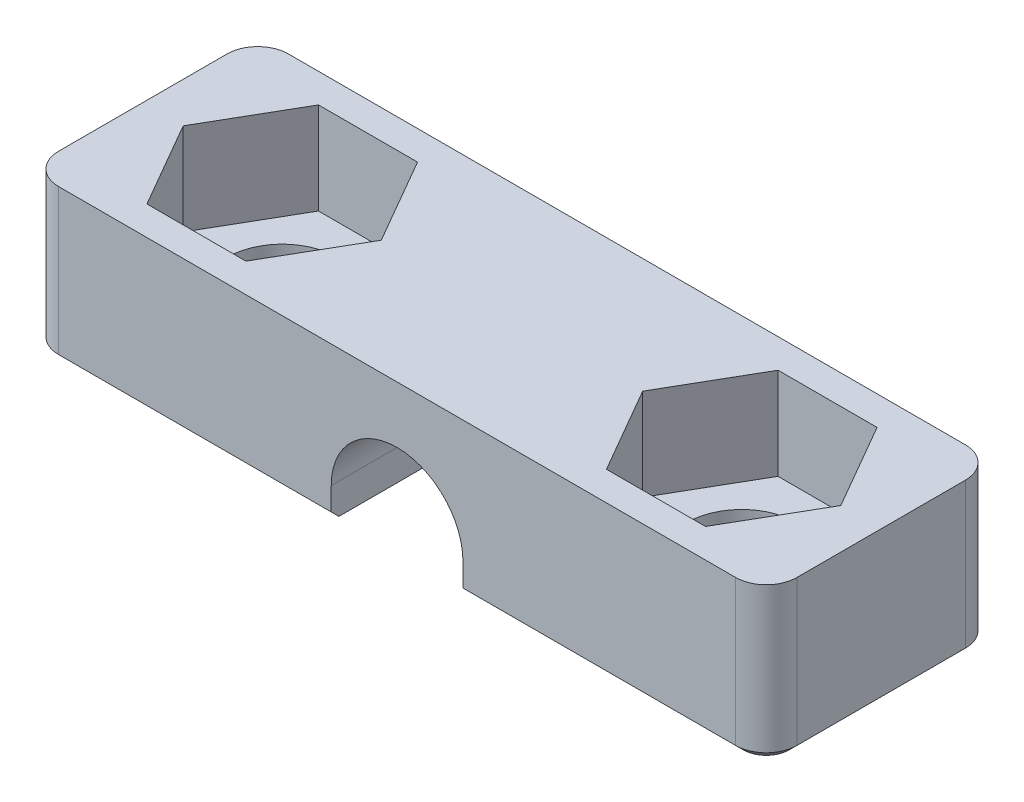
SolidWorks part; units mm, degrees
ref_plane "Front Plane" through (0, 0, 0) normal (0, 0, 1) x (1, 0, 0)
ref_plane "Top Plane" through (0, 0, 0) normal (0, 1, 0) x (1, 0, 0)
ref_plane "Right Plane" through (0, 0, 0) normal (1, 0, 0) x (0, 0, -1)
sketch "Sketch1" plane through (0, 0, 0) normal (0, 0, 1) x (1, 0, 0)
  line L0 (-2.15, 0) -> (-2.15, 1)
  line L1 (0, 0) -> (0, 7.323) construction
  line L2 (2.15, 0) -> (2.15, 1)
  line L3 (2.15, 0) -> (12.0494, 0)
  line L4 (7.5, 0) -> (7.5, 3.1149) construction
  line L5 (12.0494, 0) -> (12.0494, 5)
  line L6 (12.0494, 5) -> (-12.0494, 5)
  line L7 (-2.15, 0) -> (-12.0494, 0)
  line L8 (-12.0494, 0) -> (-12.0494, 5)
  arc A0 (-2.15, 1) -> (2.15, 1) centre (0, 1) cw
  point P16 (0, 5)
  dimension "D1" = 2.15
  dimension "D2" = 1
  dimension "D3" = 7.5
  dimension "D4" = 5
extrude "Extrude1" add sketch "Sketch1" along normal blind 7.5
sketch "Sketch2" plane through (0, 5, 0) normal (0, 1, 0) x (1, 0, 0)
  line L0 (0, 0) -> (0, -7.5) construction
  line L1 (12.0494, -7.5) -> (-12.0494, -7.5) construction
  line L2 (0, -3.75) -> (12.0494, -3.75) construction
  line L3 (12.0494, -7.5) -> (12.0494, 0) construction
  line L4 (-9.1166, -6.55) -> (-10.7332, -3.75)
  line L5 (10.7332, -3.75) -> (9.1166, -0.95)
  line L6 (9.1166, -0.95) -> (5.8834, -0.95)
  line L7 (5.8834, -0.95) -> (4.2668, -3.75)
  line L8 (4.2668, -3.75) -> (5.8834, -6.55)
  line L9 (5.8834, -6.55) -> (9.1166, -6.55)
  line L10 (9.1166, -6.55) -> (10.7332, -3.75)
  line L11 (-5.8834, -6.55) -> (-9.1166, -6.55)
  line L12 (-4.2668, -3.75) -> (-5.8834, -6.55)
  line L13 (-5.8834, -0.95) -> (-4.2668, -3.75)
  line L14 (-9.1166, -0.95) -> (-5.8834, -0.95)
  line L15 (-10.7332, -3.75) -> (-9.1166, -0.95)
  circle A0 centre (7.5, -3.75) radius 1.8
  circle A1 centre (7.5, -3.75) radius 2.8 construction
  circle A2 centre (-7.5, -3.75) radius 1.8
  dimension "D2" = 3.6
  dimension "D1" = 15
  dimension "D3" = 5.6
extrude "Extrude2" cut sketch "Sketch2" against normal through all contours A2 | A0 region at (7.5, 5, 3.75) region at (-7.5, 5, 3.75)
extrude "Extrude3" cut sketch "Sketch" against normal blind 3
sketch "Sketch" plane through (0, 5, 0) normal (0, 1, 0) x (1, 0, 0) same geometry as "Sketch2"
fillet "Fillet1" radius 1 4 edges at (12.0494, 2.5, 0) (12.0494, 2.5, 7.5) (-12.0494, 2.5, 0) (-12.0494, 2.5, 7.5)
chamfer "Chamfer1" distance 0.25 angle 45 12 edges at (-9.3, 0, 3.75) (5.7, 0, 3.75) (6.5997, 0, 0) (11.7565, 0, 0.2929) (12.0494, 0, 3.75) (11.7565, 0, 7.2071) (6.5997, 0, 7.5) (-6.5997, 0, 0) (-11.7565, 0, 0.2929) (-12.0494, 0, 3.75) (-11.7565, 0, 7.2071) (-6.5997, 0, 7.5)
